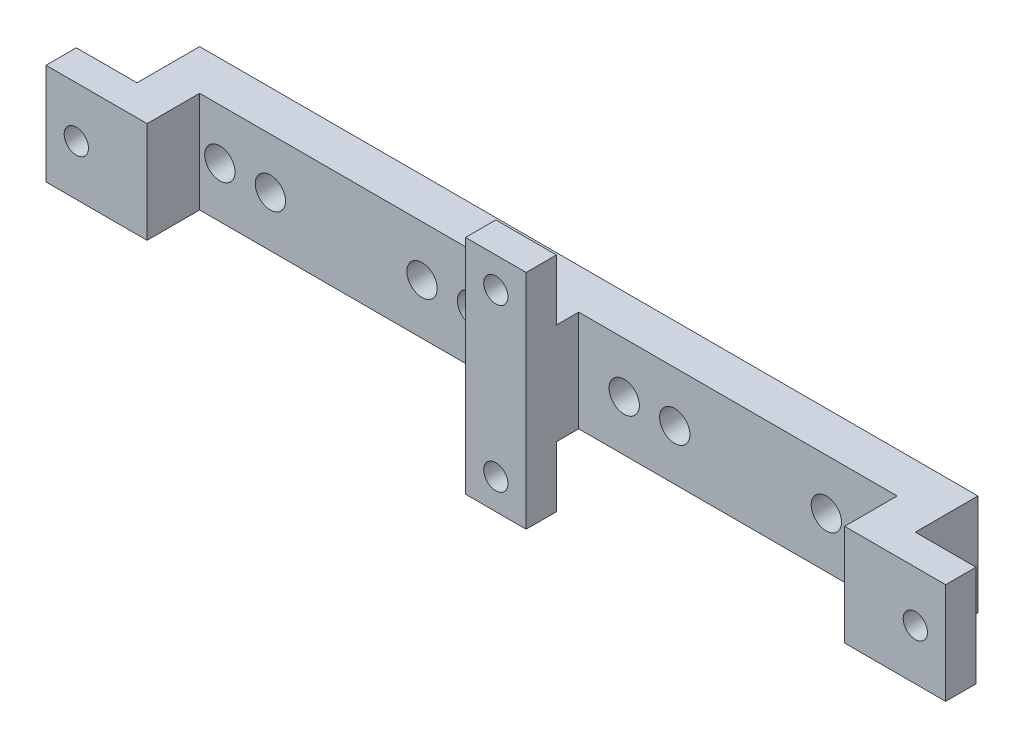
SolidWorks part; units mm, degrees
ref_plane "前视基准面" through (0, 0, 0) normal (0, 0, 1) x (1, 0, 0)
ref_plane "上视基准面" through (0, 0, 0) normal (0, 1, 0) x (1, 0, 0)
ref_plane "右视基准面" through (0, 0, 0) normal (1, 0, 0) x (0, 0, -1)
other "Configuration Table"
sketch "草图1" plane through (0, 0, 0) normal (0, 0, 1) x (1, 0, 0)
  line L0 (-16.25, 0) -> (-13.75, 0)
  line L9 (-17.25, 2.5) -> (17.25, 2.5)
  line L10 (-17.25, 2.5) -> (-17.25, -2.5)
  line L11 (-17.25, -2.5) -> (17.25, -2.5)
  line L12 (17.25, 2.5) -> (17.25, -2.5)
  line L13 (-6.25, 0) -> (-3.75, 0)
  line L14 (3.75, 0) -> (6.25, 0)
  line L15 (13.75, 0) -> (16.25, 0)
  line L16 (16.25, 0) -> (17.25, 0)
  line L17 (-16.25, 0) -> (-17.25, 0)
  line L18 (-15, 0) -> (-5, 0)
  line L19 (-5, 0) -> (5, 0)
  line L20 (5, 0) -> (15, 0)
  line L22 (17.25, 2.5) -> (19.25, 2.5)
  line L23 (17.25, 2.5) -> (17.25, -2.5)
  line L24 (17.25, -2.5) -> (19.25, -2.5)
  line L25 (19.25, 2.5) -> (19.25, -2.5)
  line L26 (-17.25, 2.5) -> (-19.25, 2.5)
  line L27 (-17.25, 2.5) -> (-17.25, -2.5)
  line L28 (-17.25, -2.5) -> (-19.25, -2.5)
  line L29 (-19.25, 2.5) -> (-19.25, -2.5)
  line L30 (-1.5, 5.5) -> (1.5, 5.5)
  line L31 (-1.5, 5.5) -> (-1.5, -5.5)
  line L32 (-1.5, -5.5) -> (1.5, -5.5)
  line L33 (1.5, 5.5) -> (1.5, -5.5)
  line L34 (-19.25, 2.5) -> (-22.25, 2.5)
  line L35 (-19.25, 2.5) -> (-19.25, -2.5)
  line L36 (-19.25, -2.5) -> (-22.25, -2.5)
  line L37 (-22.25, 2.5) -> (-22.25, -2.5)
  line L38 (19.25, 2.5) -> (22.25, 2.5)
  line L39 (19.25, 2.5) -> (19.25, -2.5)
  line L40 (19.25, -2.5) -> (22.25, -2.5)
  line L41 (22.25, 2.5) -> (22.25, -2.5)
  circle A0 centre (-16.25, 0) radius 0.75
  circle A1 centre (-13.75, 0) radius 0.75
  circle A2 centre (-6.25, 0) radius 0.75
  circle A3 centre (-3.75, 0) radius 0.75
  circle A4 centre (3.75, 0) radius 0.75
  circle A5 centre (6.25, 0) radius 0.75
  circle A6 centre (13.75, 0) radius 0.75
  circle A7 centre (16.25, 0) radius 0.75
  circle A8 centre (-20.75, 0) radius 0.6
  circle A9 centre (0, 4) radius 0.6
  circle A10 centre (0, -4) radius 0.6
  circle A11 centre (20.75, 0) radius 0.6
  point P4 (0, 2.5)
  point P6 (-17.25, 0)
  point P37 (-1.5, 0)
  point P39 (0, -5.5)
  point P54 (-20.75, 2.5)
  point P56 (20.75, 2.5)
  dimension "D4" = 1
  dimension "D1" = 5
  dimension "D2" = 10
  dimension "D3" = 1.5
  dimension "D10" = 1.2
  dimension "D5" = 2.5
  dimension "D6" = 2
  dimension "D7" = 3
  dimension "D8" = 3
  dimension "D9" = 3
  dimension "D11" = 1.5
  dimension "D12" = 1.5
extrude "凸台-拉伸1" add sketch "草图1" along normal blind 2 contours L11 L12 L9 L10
extrude "切除-拉伸1" cut sketch "草图1<9>" along normal through all contours A0 | A1 | A2 | A3 | A4 | A5 | A6 | A7
sketch "草图1<9>" plane through (0, 0, 0) normal (0, 0, 1) x (1, 0, 0) same geometry as "草图1"
extrude "凸台-拉伸2" add sketch "草图1<10>" along normal blind 4.6 contours L26 L29 L28 L10 | L25 L22 L12 L24 | L33 L9 L31 L19 | L33 L19 L31 L11 region at (-18.25, 0, 0) region at (0, 1.25, 0) region at (0, -1.25, 0) region at (18.25, 0, 0)
sketch "草图1<10>" plane through (0, 0, 0) normal (0, 0, 1) x (1, 0, 0) same geometry as "草图1"
extrude "凸台-拉伸3" add sketch "草图1<12>" against normal blind 1.5 from surface contours L34 L37 L36 L29 | L33 L30 L31 L9 | L33 L11 L31 L32 | L41 L38 L25 L40 region at (-1.4576, 4, 0) region at (-19.3083, 0, 0) region at (0, -2.5424, 0) region at (20.75, 2.4417, 0) starting at face at (-18.25, 0, 4.6)
sketch "草图1<12>" plane through (0, 0, 0) normal (0, 0, 1) x (1, 0, 0) same geometry as "草图1"
